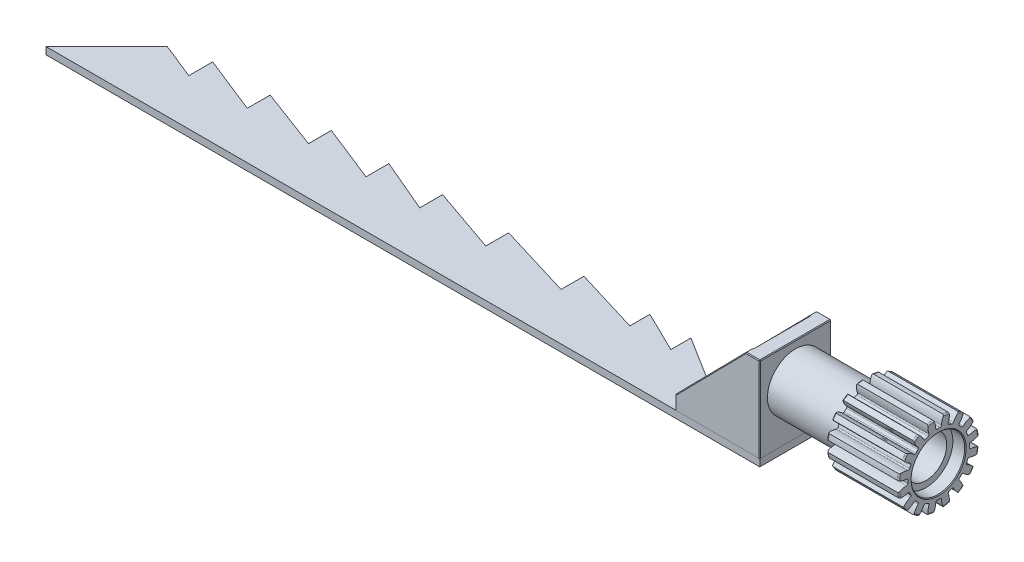
SolidWorks part; units mm, degrees
ref_plane "Front" through (0, 0, 0) normal (0, 0, 1) x (1, 0, 0)
ref_plane "Top" through (0, 0, 0) normal (0, 1, 0) x (1, 0, 0)
ref_plane "Right" through (0, 0, 0) normal (1, 0, 0) x (0, 0, -1)
sketch "Sketch1" plane through (0, 0, 0) normal (0, 0, 1) x (1, 0, 0)
  line L0 (-25.4, 0) -> (25.4, 0) construction
  line L1 (-25.4, 14.351) -> (0, 14.351)
  line L2 (-25.4, 14.351) -> (-25.4, 2)
  line L3 (-25.4, 2) -> (0, 2)
  line L8 (0, 14.351) -> (0, 2)
  dimension "OD" = 28.702
  dimension "For Shaft Diameter" = 4
  dimension "D2" = 25.4
sketch "Sketch2" plane through (0, 0, 0) normal (1, 0, 0) x (0, 0, -1)
  circle A0 centre (0, 0) radius 12.7
  circle A1 centre (0, 0) radius 2
  point P3 (8.9803, 8.9803)
  point P5 (11.7333, 4.8601)
  point P7 (0, -12.7)
  point P8 (-4.8601, -11.7333)
  point P9 (12.7, 0)
  point P10 (11.7333, -4.8601)
  point P11 (-8.9803, -8.9803)
  point P12 (-11.7333, -4.8601)
  point P13 (-12.7, 0)
  point P14 (-11.7333, 4.8601)
  point P15 (-8.9803, 8.9803)
  point P16 (-4.8601, 11.7333)
  point P17 (0, 12.7)
  point P18 (4.8601, 11.7333)
  point P19 (8.9803, -8.9803)
  point P20 (4.8601, -11.7333)
  point P26 (0, 0)
  dimension "Number of Teeth" = 16
sketch "Sketch12" plane through (0, 0, 0) normal (0, 0, 1) x (1, 0, 0)
  line L0 (-25.4, 14.351) -> (-25.4, 2) construction
  line L1 (-25.4, 14.351) -> (0, 14.351) construction
  line L5 (-25.4, 2) -> (0, 2) construction
  line L6 (-25.4, 14.351) -> (-25.4, 2)
  line L7 (-25.4, 14.351) -> (0, 14.351)
  line L11 (-25.4, 2) -> (0, 2)
  line L12 (0, 0) -> (25.4, 0) construction
  line L13 (0, 14.351) -> (0, 2) construction
  line L14 (0, 14.351) -> (0, 2)
revolve "Revolve3" add sketch "Sketch12" angle 360 about L12 region at (-12.7, 8.1755, 0)
sketch "Sketch6" plane through (-25.4, 0, 0) normal (-1, 0, 0) x (0, 0, -1)
  line L0 (-11.7799, 1.0374) -> (-12.651, 1.1141) construction
  line L1 (0, 0) -> (-10.9511, 0) construction
  line L2 (-12.651, 1.1141) -> (-17.3011, 3.2857) construction
  line L3 (0, 0) -> (-14.0752, -2.7997) construction
  line L4 (-17.3011, 3.2857) -> (-17.3011, -3.2857) construction
  line L5 (-17.3011, -3.2857) -> (-12.651, -1.1141) construction
  line L6 (-12.651, -1.1141) -> (-11.7799, -1.0374) construction
  line L7 (-10.9511, 0) -> (-14.351, 0) construction
  line L8 (-10.9089, -0.9607) -> (-10.9089, 0.9607) construction
  line L9 (-10.9089, -0.9607) -> (-11.7799, -1.0374)
  line L10 (-10.9089, 0.9607) -> (-11.7799, 1.0374)
  line L11 (-12.651, -1.1141) -> (-12.651, 1.1141) construction
  line L12 (-10.9089, -0.9607) -> (-12.651, -0.9607) construction
  circle A0 centre (0, 0) radius 12.7 construction
  circle A1 centre (0, 0) radius 10.9511 construction
  arc A2 (-10.9089, 0.9607) -> (-10.9089, -0.9607) centre (0, 0) ccw
  circle A4 centre (0, 0) radius 14.351 construction
  circle A6 centre (0, 0) radius 14.351 construction
  arc A7 (-13.8564, -3.735) -> (-14.231, -1.852) centre (0, 0) cw construction
  arc A8 (-14.231, -1.852) -> (-11.7799, -1.0374) centre (-11.2893, -6.6087) cw
  arc A9 (-11.7799, 1.0374) -> (-14.231, 1.852) centre (-11.2893, 6.6087) cw
  arc A10 (-14.231, 1.852) -> (-14.231, -1.852) centre (0, 0) ccw
  point P1 (-11.7799, -0.9607)
  point P7 (-12.651, 0)
  point P21 (-10.9089, -0.9607)
  point P24 (-10.9089, 0.9607)
  point P32 (-12.651, 0)
  dimension "D4" = 6.35
  dimension "D2" = 11.25
  dimension "D3" = 20
  dimension "D6" = 2.2282
sketch "Sketch7" plane through (0, 0, 0) normal (0, 0, 1) x (1, 0, 0)
  line L0 (-25.4, 0) -> (11.9126, 0)
  line L3 (-25.4, 0) -> (25.4, 0) construction
fillet "Fillet1" radius 0.4445 2 edges at (-25.4, -14.351, 0) (0, -14.351, 0)
sweep "Cut-Sweep1" cut profiles "Sketch6" path "Sketch7" parameters "D1"=0
fillet "Fillet2" radius 0.4456 2 edges
pattern_circular "CirPattern4" count 16 over 360 about axis through (-25.4, 0, 0) along (1, 0, 0) of "Cut-Sweep1", "Fillet2"
sketch "Sketch13" plane through (0, 0, 0) normal (1, 0, 0) x (0, 0, -1)
  circle A0 centre (0, 0) radius 10
  circle A1 centre (0, 7) radius 1.5
  circle A2 centre (7, 0) radius 1.5
  circle A3 centre (0, -7) radius 1.5
  circle A4 centre (-7, 0) radius 1.5
  point P14 (0, 0)
  dimension "D1" = 20
  dimension "D3" = 3
  dimension "D2" = 7
  dimension "D4" = 4
extrude "Boss-Extrude1" add sketch "Sketch13" against normal blind 25.4 from surface contours A0 starting at face at (-25.4, -2, 0)
sketch "Sketch15" plane through (0, 0, 0) normal (1, 0, 0) x (0, 0, -1)
  line L0 (12.7, -12.7) -> (12.7, -17.7)
  line L1 (12.7, 12.7) -> (-12.7, 12.7)
  line L2 (12.7, 12.7) -> (12.7, -12.7)
  line L3 (12.7, -12.7) -> (-12.7, -12.7)
  line L4 (-12.7, 12.7) -> (-12.7, -12.7)
  line L5 (12.7, 12.7) -> (-12.7, -12.7) construction
  line L6 (12.7, -12.7) -> (-12.7, 12.7) construction
  line L7 (12.7, -17.7) -> (-12.7, -17.7)
  line L8 (-12.7, -17.7) -> (-12.7, -12.7)
  point P0 (0, 0)
  dimension "D1" = 25.4
  dimension "D2" = 5
extrude "Boss-Extrude2" add sketch "Sketch15" against normal blind 5 from surface contours L1 L4 L3 L2 region at (0, 0, 0) starting at face at (-50.8, 10, 0)
extrude "Boss-Extrude3" add sketch "Sketch15<3>" against normal blind 30 from surface contours L8 L7 L0 L3 region at (0, -15.2, 0) starting at face at (-50.8, 10, 0)
sketch "Sketch15<3>" plane through (0, 0, 0) normal (1, 0, 0) x (0, 0, -1) same geometry as "Sketch15"
sketch "Sketch16" plane through (0, 0, 12.7) normal (0, 0, 1) x (1, 0, 0)
  line L0 (-80.8, -12.7) -> (-55.8, 12.7)
rib "Rib1" sketch "Sketch16" sketch "Sketch16" thickness 2.54 extrusion direction parallel to sketch draft on no parameters "D1"=2.54
sketch "Sketch17" plane through (0, 0, -12.7) normal (0, 0, -1) x (-1, 0, 0)
  line L0 (55.8, 12.7) -> (80.8, -12.7)
rib "Rib2" sketch "Sketch17" sketch "Sketch17" thickness 2.54 extrusion direction parallel to sketch draft on no parameters "D1"=2.54
sketch "Sketch18" plane through (0, 0, 0) normal (1, 0, 0) x (0, 0, -1)
  circle A0 centre (0, 0) radius 9.525
  circle A1 centre (0, 0) radius 7.35
  dimension "D1" = 19.05
  dimension "D2" = 14.7
extrude "Cut-Extrude1" cut sketch "Sketch18" against normal through all contours A1
extrude "Cut-Extrude2" cut sketch "Sketch18<3>" against normal blind 4.4688 contours A0
sketch "Sketch18<3>" plane through (0, 0, 0) normal (1, 0, 0) x (0, 0, -1) same geometry as "Sketch18"
extrude "Cut-Extrude3" cut sketch "Sketch18<4>" along normal blind 12.7 from surface contours A0 starting at face at (-55.8, -7.35, 0)
sketch "Sketch18<4>" plane through (0, 0, 0) normal (1, 0, 0) x (0, 0, -1) same geometry as "Sketch18"
chamfer "Chamfer1" distance 0.26 angle 45 17 edges at (-80.8, -17.7, 0) (-50.8, -17.7, 0) (-53.3, 12.7, -12.7) (-68.3, 0, -12.7) (-80.8, -15.2, -12.7) (-65.8, -17.7, -12.7) (-50.8, -2.5, -12.7) (-65.8, -17.7, 12.7) (-80.8, -15.2, 12.7) (-68.3, 0, 12.7) (-53.3, 12.7, 12.7) (-50.8, -2.5, 12.7) (-50.8, 12.7, 0) (-80.8, -12.7, 0) (-55.8, 12.7, 0) (0, 0, -9.525) (-55.8, -9.525, 0)
sketch "Sketch19" plane through (0, -17.7, 0) normal (0, -1, 0) x (1, 0, 0)
  line L0 (-80.54, -12.44) -> (-51.06, -12.44) construction
  line L1 (-51.06, 12.44) -> (-305.06, 12.44)
  line L2 (-51.06, 12.44) -> (-51.06, -12.44)
  line L3 (-51.06, -12.44) -> (-305.06, -12.44)
  line L4 (-305.06, 12.44) -> (-305.06, -12.44)
  line L5 (-85.1908, -12.44) -> (-85.1908, -2.9161)
  line L6 (-85.1908, -2.9161) -> (-100.4163, -12.44)
  line L7 (-100.4163, -12.44) -> (-100.4163, -5.3232)
  line L8 (-100.4163, -5.3232) -> (-114.9726, -12.44)
  line L9 (-114.9726, -12.44) -> (-114.9726, -5.3232)
  line L10 (-114.9726, -5.3232) -> (-138.3965, -12.44)
  line L11 (-138.3965, -12.44) -> (-138.3965, -4.3193)
  line L12 (-138.3965, -4.3193) -> (-165.1245, -12.44)
  line L13 (-165.1245, -12.44) -> (-165.1245, -4.3193)
  line L14 (-165.1245, -4.3193) -> (-188.5905, -12.44)
  line L15 (-188.5905, -12.44) -> (-188.5905, -4.3193)
  line L16 (-188.5905, -4.3193) -> (-207.6642, -12.44)
  line L17 (-207.6642, -12.44) -> (-207.6642, -4.3193)
  line L18 (-207.6642, -4.3193) -> (-228.0764, -12.44)
  line L19 (-228.0764, -12.44) -> (-228.0764, -4.3193)
  line L20 (-228.0764, -4.3193) -> (-249.8271, -12.44)
  line L21 (-249.8271, -12.44) -> (-249.8271, -4.3193)
  line L22 (-249.8271, -4.3193) -> (-270.2394, -12.44)
  line L23 (-270.2394, -12.44) -> (-270.2394, -3.9865)
  line L24 (-270.2394, -3.9865) -> (-291.4882, -12.44)
  point P21 (-291.4882, -12.44)
  point P29 (-85.1908, -12.44)
  line M3 (-80.54, 12.44) -> (-80.54, -12.44)
  line M4 (-80.54, -12.44) -> (-51.06, -12.44)
  line M5 (-51.06, -12.44) -> (-51.06, 12.44)
  line M6 (-51.06, 12.44) -> (-80.54, 12.44)
  dimension "D1" = 254
extrude "Boss-Extrude4" add sketch "Sketch19" along normal blind 2.54 contours L24 L23 L22 L21 L20 L19 L18 L17 L16 L15 L14 L13 L12 L11 L10 L9 L8 L7 L6 L5 L3 L1 L4 M3 | M6 M3 M4 M5 region at (-65.8, -17.7, 0) region at (-194.0693, -17.7, 1.7056)
chamfer "Chamfer2" distance 25.4 angle 45 1 edges at (-305.06, -18.97, -12.44)
equation "\"D1@CirPattern4\" = \"Number of Teeth@Sketch2\""
equation "\"D1@Sketch2\" = \"For Shaft Diameter@Sketch1\""
equation "\"D2@Sketch6\" = 360 / \"Number of Teeth@Sketch2\" / 2"
equation "\"D1@Chamfer1\"=\"For Shaft Diameter@Sketch1\" * 0.065"
